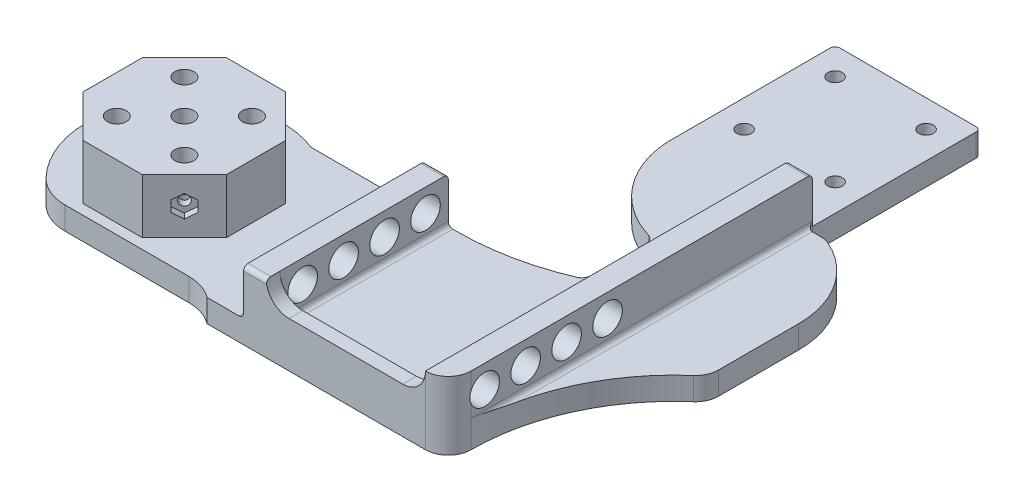
SolidWorks part; units mm, degrees
ref_plane "Спереди" through (0, 0, 0) normal (0, 0, 1) x (1, 0, 0)
ref_plane "Сверху" through (0, 0, 0) normal (0, 1, 0) x (1, 0, 0)
ref_plane "Справа" through (0, 0, 0) normal (1, 0, 0) x (0, 0, -1)
sketch "Эскиз2" plane through (0, 0, 0) normal (0, 1, 0) x (1, 0, 0)
  line L0 (0, 0) -> (32, 0)
  line L1 (0, 0) -> (0, 88)
  line L2 (32, 0) -> (32, 88)
  line L3 (0, 88) -> (32, 88)
  dimension "D1" = 88
  dimension "D2" = 32
extrude "Бобышка-Вытянуть1" add sketch "Эскиз2" along normal blind 5
sketch "Эскиз9" plane through (0, 5, 0) normal (0, 1, 0) x (1, 0, 0)
  line L0 (32, 10) -> (32, -30)
  line L1 (32, 10) -> (-68, 10)
  line L2 (32, -30) -> (-68, -30)
  line L3 (-68, 10) -> (-68, -30)
  line L4 (32, 0) -> (32, 88) construction
  line L5 (-68, -10) -> (32, -10) construction
  line L6 (32, 88) -> (0, 88) construction
  dimension "D1" = 98
  dimension "D2" = 40
  dimension "D3" = 100
extrude "Бобышка-Вытянуть6" add sketch "Эскиз9" against normal blind 5
sketch "Эскиз11" plane through (0, 5, 0) normal (0, 1, 0) x (1, 0, 0)
  line L0 (-46, -10) -> (-46, -20.5) construction
  line L1 (-46, -10) -> (-46, 0.5) construction
  line L2 (-46, -10) -> (-53.4246, -2.5754) construction
  line L3 (-46, -10) -> (-53.4246, -17.4246) construction
  line L6 (-68, -10) -> (32, -10) construction
  line L7 (-68, 10) -> (-68, -30) construction
  line L8 (32, -30) -> (32, 88) construction
  circle A0 centre (-46, -10) radius 10.5 construction
  circle A1 centre (-53.4246, -2.5754) radius 2.1
  circle A2 centre (-38.5754, -2.5754) radius 2.1
  circle A3 centre (-38.5754, -17.4246) radius 2.1
  circle A4 centre (-53.4246, -17.4246) radius 2.1
  circle A5 centre (-46, -10) radius 2.1
  point P22 (-46, -10)
  dimension "D1" = 22
  dimension "D3" = 21
  dimension "D4" = 4.2
  dimension "D5" = 4
  dimension "D2" = 45
  dimension "D7" = 4.2
extrude "Вырез-Вытянуть3" cut sketch "Эскиз11" against normal up to surface (5 mm away) up to face at (-12, 0, -22.6667)
sketch "Эскиз12" plane through (0, 0, 0) normal (0, -1, 0) x (1, 0, 0)
  circle A0 centre (-53.4246, 2.5754) radius 2.1 construction
  circle A1 centre (-53.4246, 2.5754) radius 2.1 construction
  circle A2 centre (-38.5754, 2.5754) radius 2.1 construction
  circle A3 centre (-38.5754, 2.5754) radius 2.1 construction
  circle A8 centre (-46, 10) radius 19.5
  circle A9 centre (-46, 10) radius 21.5
  circle A10 centre (-38.5754, 17.4246) radius 2.1 construction
  circle A11 centre (-38.5754, 17.4246) radius 2.1 construction
  circle A12 centre (-53.4246, 17.4246) radius 2.1 construction
  circle A13 centre (-53.4246, 17.4246) radius 2.1 construction
  circle A14 centre (-46, 10) radius 10.5 construction
  dimension "D1" = 39
  dimension "D2" = 43
extrude "Бобышка-Вытянуть7" add sketch "Эскиз12" along normal blind 8
sketch "Эскиз13" plane through (0, 5, 0) normal (0, 1, 0) x (1, 0, 0)
  line L0 (6, 81) -> (26, 81) construction
  line L1 (6, 81) -> (6, 61) construction
  line L2 (26, 81) -> (26, 61) construction
  line L3 (6, 61) -> (26, 61) construction
  line L4 (16, 81) -> (16, 61) construction
  line L5 (16, 88) -> (16, -30) construction
  line L6 (32, 88) -> (0, 88) construction
  line L7 (-68, -30) -> (32, -30) construction
  circle A0 centre (6, 81) radius 1.6
  circle A1 centre (6, 61) radius 1.6
  circle A2 centre (26, 61) radius 1.6
  circle A3 centre (26, 81) radius 1.6
  dimension "D4" = 3.2
  dimension "D5" = 3.2
  dimension "D6" = 3.2
  dimension "D7" = 3.2
  dimension "D1" = 20
  dimension "D2" = 20
  dimension "D3" = 7
extrude "Вырез-Вытянуть4" cut sketch "Эскиз13" against normal through all
sketch "Sketch1" plane through (0, 0, -88) normal (0, 0, -1) x (-1, 0, 0)
  line L4 (-32, 0) -> (0, 0)
  line L5 (0, 0) -> (0, 5)
  line L6 (0, 5) -> (-32, 5)
  line L7 (-32, 5) -> (-32, 0)
  line L8 (-32, 0) -> (0, 0)
  line L9 (0, 0) -> (0, 5)
  line L10 (0, 5) -> (-32, 5)
  line L11 (-32, 5) -> (-32, 0)
  dimension "D1" = 0
extrude "Cut-Extrude1" cut sketch "Sketch1" against normal blind 1
sketch "Эскиз14" plane through (0, 0, 0) normal (0, -1, 0) x (1, 0, 0)
  line L3 (-53.8899, 30) -> (-68, 30)
  line L4 (-68, 30) -> (-68, -10)
  line L5 (-68, -10) -> (-53.8899, -10)
  line L6 (-53.8899, 30) -> (-68, 30)
  line L7 (-68, 30) -> (-68, -10)
  line L8 (-68, -10) -> (-53.8899, -10)
  arc A1 (-53.8899, 30) -> (-53.8899, -10) centre (-46, 10) ccw
  arc A2 (-53.8899, 30) -> (-53.8899, -10) centre (-46, 10) ccw
  dimension "D1" = 0
extrude "Вырез-Вытянуть5" cut sketch "Эскиз14" against normal through all
sketch "Эскиз15" plane through (0, 0, 0) normal (0, 1, 0) x (1, 0, 0)
  line L1 (-38.1101, -30) -> (-53.8899, -30)
  line L2 (-38.1101, -30) -> (-53.8899, -30)
  line L3 (-53.8899, 10) -> (-38.1101, 10)
  line L4 (-53.8899, 10) -> (-38.1101, 10)
  arc A1 (-53.8899, -30) -> (-38.1101, -30) centre (-46, -10) ccw
  arc A2 (-53.8899, -30) -> (-38.1101, -30) centre (-46, -10) ccw
  arc A3 (-38.1101, 10) -> (-53.8899, 10) centre (-46, -10) ccw
  arc A4 (-38.1101, 10) -> (-53.8899, 10) centre (-46, -10) ccw
  dimension "D1" = 0
  dimension "D2" = 0
extrude "Бобышка-Вытянуть8" add sketch "Эскиз15" along normal up to surface (5 mm away) up to face at (-53.4246, 5, 4.6754)
sketch "Эскиз16" plane through (0, 5, 0) normal (0, 1, 0) x (1, 0, 0)
  line L0 (-13, 10) -> (-8, 10)
  line L1 (-13, 10) -> (-13, -30)
  line L2 (-8, 10) -> (-8, -30)
  line L3 (-13, -30) -> (-8, -30)
  line L4 (0, 10) -> (-38.1101, 10) construction
  line L5 (-38.1101, -30) -> (32, -30) construction
  line L6 (32, -30) -> (32, 87) construction
  line L7 (27, -30) -> (32, -30)
  line L8 (27, -30) -> (27, 50)
  line L9 (32, -30) -> (32, 50)
  line L10 (27, 50) -> (32, 50)
  dimension "D1" = 5
  dimension "D2" = 45
  dimension "D3" = 5
  dimension "D4" = 80
extrude "Бобышка-Вытянуть9" add sketch "Эскиз16" along normal blind 10
sketch "Эскиз17" plane through (0, 5, 0) normal (0, 1, 0) x (1, 0, 0)
  line L0 (-8, -30) -> (-8, -27)
  line L1 (-8, -30) -> (27, -30)
  line L2 (-8, -27) -> (27, -27)
  line L3 (27, -30) -> (27, -27)
  line L4 (-8, -30) -> (-8, 10) construction
  line L5 (27, 50) -> (27, -30) construction
  dimension "D1" = 3
extrude "Бобышка-Вытянуть10" add sketch "Эскиз17" along normal blind 5
sketch "Эскиз18" plane through (-8, 0, 0) normal (1, 0, 0) x (0, 0, -1)
  line L0 (10, 10) -> (-41.8716, 10) construction
  line L1 (10, 15) -> (10, 5) construction
  circle A0 centre (5, 10) radius 3.25
  circle A1 centre (-4, 10) radius 3.25
  circle A2 centre (-13, 10) radius 3.25
  circle A3 centre (-22, 10) radius 3.25
  dimension "D1" = 6.5
  dimension "D2" = 6.5
  dimension "D3" = 6.5
  dimension "D4" = 6.5
  dimension "D5" = 5
  dimension "D6" = 9
  dimension "D7" = 9
  dimension "D8" = 9
extrude "Вырез-Вытянуть6" cut sketch "Эскиз18" against normal through all
sketch "Эскиз19" plane through (32, 0, 0) normal (1, 0, 0) x (0, 0, -1)
  line L0 (50, 10) -> (-21.4049, 10) construction
  line L1 (50, 15) -> (50, 5) construction
  circle A0 centre (41, 10) radius 3.25
  circle A1 centre (32, 10) radius 3.25
  circle A2 centre (23, 10) radius 3.25
  circle A3 centre (14, 10) radius 3.25
  dimension "D1" = 6.5
  dimension "D2" = 6.5
  dimension "D3" = 6.5
  dimension "D4" = 6.5
  dimension "D5" = 9
  dimension "D6" = 9
  dimension "D7" = 9
  dimension "D8" = 9
fillet "Скругление5" radius 1 4 edges at (27, 5, -11.5) (9.5, 5, 27)
fillet "Скругление6" radius 5 2 edges at (27, 10, 28.5) (-8, 10, 28.5)
fillet "Скругление7" radius 1 2 edges at (32, 2.5, -87) (0, 2.5, -87)
fillet "Скругление8" radius 1 3 edges at (-10.5, 15, 30) (-10.5, 15, -10) (29.5, 15, -50)
sketch "Эскиз20" plane through (0, -8, 0) normal (0, -1, 0) x (1, 0, 0)
  circle A1 centre (-46, 10) radius 21.5
  circle A2 centre (-46, 10) radius 21.5
  dimension "D1" = 0
extrude "Вырез-Вытянуть8" cut sketch "Эскиз20" against normal up to surface (8 mm away) up to face at (26, 0, -82.6)
sketch "Эскиз21" plane through (0, 5, 0) normal (0, 1, 0) x (1, 0, 0)
  line L0 (-57.758, -28) -> (-27, -28)
  line L1 (-38.1101, -30) -> (-14, -30) construction
  line L2 (-13, 10) -> (-13, -30) construction
  line L3 (-38.1101, -30) -> (-21, -30)
  arc A0 (-38.1101, 10) -> (-38.1101, -30) centre (-46, -10) ccw construction
  arc A1 (-27, -28) -> (-21, -30) centre (-27, -38) cw
  arc A2 (-57.758, -28) -> (-38.1101, -30) centre (-46, -10) ccw
  dimension "D1" = 2
  dimension "D2" = 10
  dimension "D3" = 8
extrude "Вырез-Вытянуть9" cut sketch "Эскиз21" against normal through all
fillet "Скругление9" radius 10 1 edges at (-57.758, 2.5, 28)
sketch "Эскиз22" plane through (0, 0, 0) normal (-1, 0, 0) x (0, 0, 1)
  line L0 (-50, 14) -> (-50, 6) construction
  line L1 (-50, 5) -> (-50, 0) construction
  line L2 (-86, 5) -> (-10, 5) construction
  line L3 (-86, 0) -> (-10, 0) construction
  line L4 (-50, 5) -> (-10, 5)
  line L5 (-50, 0) -> (-10, 0)
  line L6 (-10, 0) -> (-10, 5) construction
  line L7 (-10, 0) -> (-10, 5)
  line L8 (-50, 5) -> (-50, 0)
extrude "Вырез-Вытянуть10" cut sketch "Эскиз22" against normal blind 17
sketch "Эскиз23" plane through (32, 0, 0) normal (1, 0, 0) x (0, 0, -1)
  line L4 (10, 5) -> (10, 0)
  line L5 (50, 5) -> (10, 5)
  line L6 (50, 0) -> (50, 5)
  line L7 (10, 0) -> (50, 0)
  line L8 (10, 5) -> (10, 0)
  line L9 (50, 5) -> (10, 5)
  line L10 (50, 0) -> (50, 5)
  line L11 (10, 0) -> (50, 0)
  dimension "D1" = 0
extrude "Бобышка-Вытянуть11" add sketch "Эскиз23" along normal blind 17
sketch "Эскиз25" plane through (0, 5, 0) normal (0, 1, 0) x (1, 0, 0)
  line L0 (17, 15) -> (17, 10)
  line L1 (17, 10) -> (17, 50) construction
  line L2 (17, 10) -> (-6, 10)
  line L3 (17, 10) -> (-7, 10) construction
  line L6 (17, 30) -> (17, 50)
  line L7 (17, 50) -> (0, 50)
  arc A0 (17, 30) -> (0, 50) centre (21.9531, 51.4352) cw
  arc A1 (17, 15) -> (-6, 10) centre (-6, 65.4) cw
  dimension "D4" = 22
  dimension "D1" = 5
  dimension "D2" = 23
  dimension "D3" = 15
  dimension "D5" = 20
extrude "Бобышка-Вытянуть12" add sketch "Эскиз25" against normal up to surface (5 mm away) up to face at (4.4666, 0, -26.743)
fillet "Скругление10" radius 2 2 edges at (17, 2.5, -15) (17, 2.5, -30)
sketch "Эскиз26" plane through (0, 5, 0) normal (0, 1, 0) x (1, 0, 0)
  line L0 (32, 30) -> (49, 30) construction
  line L1 (32, 50) -> (32, 10) construction
  line L3 (49, 50) -> (49, 10) construction
  line L4 (32, 50) -> (32, 30) construction
  line L5 (49, 50) -> (32, 50) construction
  line L6 (49, 50) -> (32, 50)
  line L7 (49, 50) -> (49, 30)
  arc A0 (49, 30) -> (32, 50) centre (28.7353, 30) ccw
  dimension "D1" = 20
extrude "Вырез-Вытянуть11" cut sketch "Эскиз26" against normal through all
sketch "Эскиз27" plane through (0, 5, 0) normal (0, 1, 0) x (1, 0, 0)
  line L0 (49, 10) -> (32, 10) construction
  line L1 (49, 10) -> (32, 10)
  line L2 (32, 10) -> (32, -25)
  arc A0 (49, 10) -> (32, -25) centre (76.5294, -25) ccw
  dimension "D1" = 35
extrude "Бобышка-Вытянуть13" add sketch "Эскиз27" against normal up to surface (5 mm away) up to face at (5.1363, 0, -23.6939)
fillet "Скругление12" radius 5 1 edges at (32, 7.5, 30)
fillet "Скругление13" radius 1 1 edges at (32, 5, -12.5)
sketch "Эскиз28" plane through (32, 0, 0) normal (1, 0, 0) x (0, 0, -1)
  circle A0 centre (5, 10) radius 3.25 construction
  circle A1 centre (-4, 10) radius 3.25 construction
  circle A2 centre (-13, 10) radius 3.25 construction
  circle A3 centre (-22, 10) radius 3.25 construction
  circle A4 centre (5, 10) radius 3.25
  circle A5 centre (-4, 10) radius 3.25
  circle A6 centre (-13, 10) radius 3.25
  circle A7 centre (-22, 10) radius 3.25
extrude "Вырез-Вытянуть12" cut sketch "Эскиз28" against normal up to surface (5 mm away) up to face at (27, 11.2414, -19.0414)
fillet "Скругление14" radius 5 1 edges at (49, 2.5, -10)
sketch "Эскиз29" plane through (0, 0, -50) normal (0, 0, -1) x (-1, 0, 0)
  line L0 (-32, 0) -> (-32, 5) construction
  line L1 (-32, 0) -> (-32, 8)
  line L2 (-32, 14) -> (-32, 6) construction
  line L3 (-32, 8) -> (-37, 8)
  line L4 (-37, 8) -> (-37, 0)
  line L5 (-37, 0) -> (-32, 0)
  dimension "D1" = 5
  dimension "D2" = 8
extrude "Вырез-Вытянуть13" cut sketch "Эскиз29" against normal blind 1
fillet "Скругление15" radius 1 1 edges at (32, 3, -49)
fillet "Скругление16" radius 5 1 edges at (35.7822, 2.5, -49)
sketch "Эскиз33" plane through (0, 5, 0) normal (0, 1, 0) x (1, 0, 0)
  line L0 (-46, -10) -> (-46, 5.75) construction
  line L1 (-52.5239, -25.75) -> (-39.4761, -25.75)
  line L2 (-39.4761, -25.75) -> (-30.25, -16.5239)
  line L3 (-30.25, -16.5239) -> (-30.25, -3.4761)
  line L4 (-30.25, -3.4761) -> (-39.4761, 5.75)
  line L5 (-39.4761, 5.75) -> (-52.5239, 5.75)
  line L6 (-52.5239, 5.75) -> (-61.75, -3.4761)
  line L7 (-61.75, -3.4761) -> (-61.75, -16.5239)
  line L8 (-61.75, -16.5239) -> (-52.5239, -25.75)
  line L9 (-27, -28) -> (-54.2614, -28) construction
  circle A0 centre (-46, -10) radius 15.75 construction
  circle A2 centre (-53.4246, -2.5754) radius 2.1 construction
  circle A3 centre (-46, -10) radius 2.1 construction
  circle A4 centre (-53.4246, -17.4246) radius 2.1 construction
  circle A5 centre (-38.5754, -2.5754) radius 2.1 construction
  circle A6 centre (-38.5754, -17.4246) radius 2.1 construction
  circle A7 centre (-53.4246, -2.5754) radius 2.1
  circle A8 centre (-46, -10) radius 2.1
  circle A9 centre (-53.4246, -17.4246) radius 2.1
  circle A10 centre (-38.5754, -2.5754) radius 2.1
  circle A11 centre (-38.5754, -17.4246) radius 2.1
  dimension "D1" = 2.25
extrude "Бобышка-Вытянуть15" add sketch "Эскиз33" along normal blind 12
sketch "Эскиз37" plane through (-6.8631, 0, -6.8631) normal (0.7071, 0, 0.7071) x (0.7071, 0, -0.7071)
  line L0 (-39.598, 17) -> (-39.598, 5) construction
  line L1 (-46.1218, 17) -> (-33.0741, 17) construction
  line L2 (-46.1218, 5) -> (-33.0741, 5) construction
  circle A0 centre (-39.598, 11) radius 1.1
  dimension "D1" = 2.2
extrude "Вырез-Вытянуть15" cut sketch "Эскиз37" against normal up to surface (3.4611 mm away) up to face at (-38.5754, 0, 15.3246)
sketch "Эскиз38" plane through (-6.8631, 0, -6.8631) normal (0.7071, 0, 0.7071) x (0.7071, 0, -0.7071)
  line L0 (-39.598, 11) -> (-39.598, 13.4249) construction
  line L1 (-39.598, 8.5751) -> (-37.498, 9.7876)
  line L2 (-37.498, 9.7876) -> (-37.498, 12.2124)
  line L3 (-37.498, 12.2124) -> (-39.598, 13.4249)
  line L4 (-39.598, 13.4249) -> (-41.698, 12.2124)
  line L5 (-41.698, 12.2124) -> (-41.698, 9.7876)
  line L6 (-41.698, 9.7876) -> (-39.598, 8.5751)
  circle A0 centre (-39.598, 11) radius 2.1 construction
  dimension "D1" = 4.2
extrude "Вырез-Вытянуть16" cut sketch "Эскиз38" against normal blind 1.6
